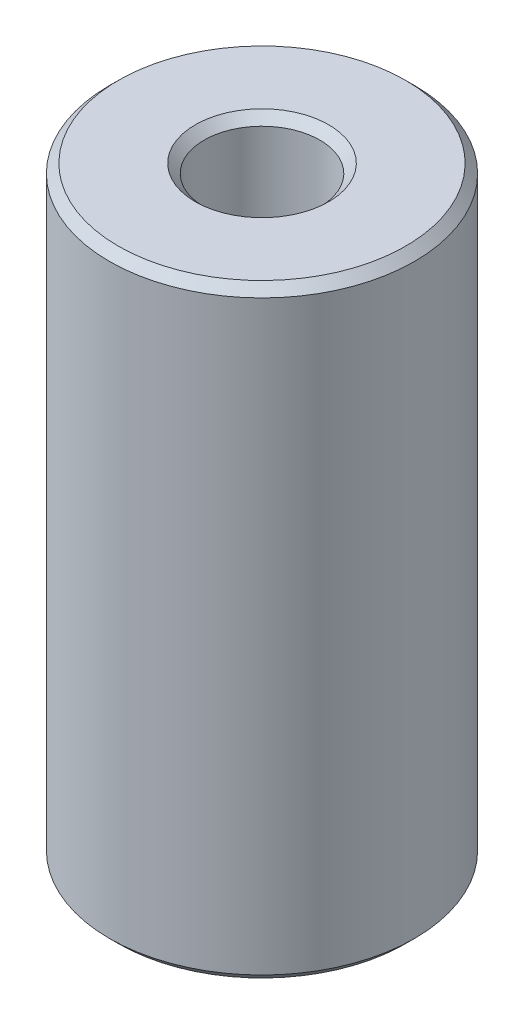
SolidWorks part; units mm, degrees
ref_plane "Front Plane" through (0, 0, 0) normal (0, 0, 1) x (1, 0, 0)
ref_plane "Top Plane" through (0, 0, 0) normal (0, 1, 0) x (1, 0, 0)
ref_plane "Right Plane" through (0, 0, 0) normal (1, 0, 0) x (0, 0, -1)
sketch "Sketch1" plane through (0, 0, 0) normal (0, 1, 0) x (1, 0, 0)
  circle A0 centre (0, 0) radius 5
  dimension "SLEEVE_OD" = 10
extrude "Boss-Extrude1" add sketch "Sketch1" along normal blind 19.8084
sketch "Sketch2" plane through (0, 0, 0) normal (0, 1, 0) x (1, 0, 0)
  circle A0 centre (0, 0) radius 1.8979
  dimension "BORE_D" = 3.7958
extrude "Cut-Extrude1" cut sketch "Sketch2" along normal through all
chamfer "Chamfer1" distance 0.2899 angle 45 4 edges at (0, 19.8084, 1.8979) (0, 0, 1.8979) (0, 0, 5) (0, 19.8084, 5)
